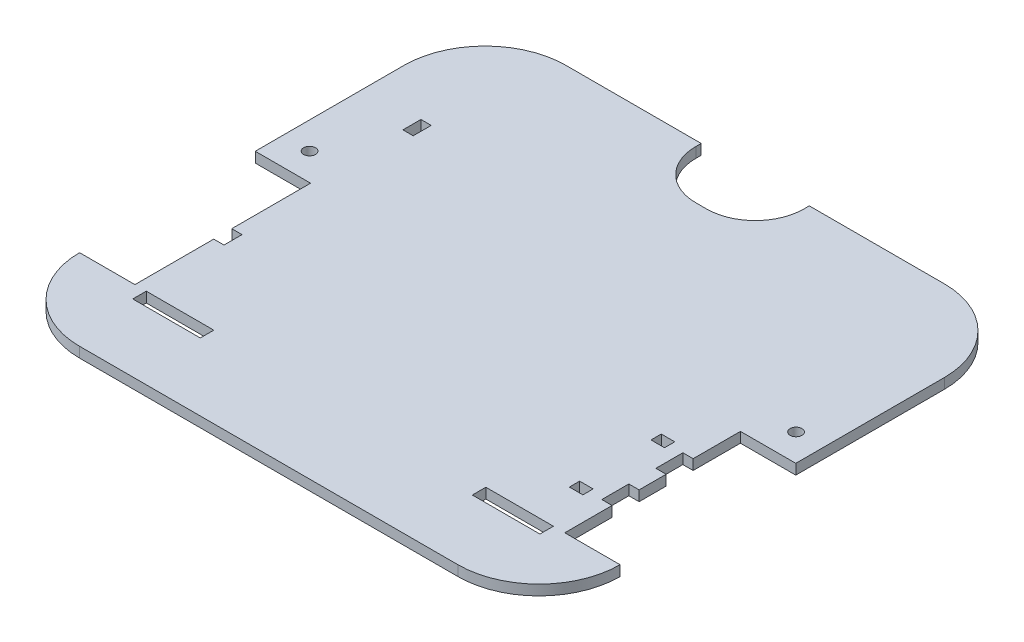
SolidWorks part; units mm, degrees
ref_plane "Front Plane" through (0, 0, 0) normal (0, 0, 1) x (1, 0, 0)
ref_plane "Top Plane" through (0, 0, 0) normal (0, 1, 0) x (1, 0, 0)
ref_plane "Right Plane" through (0, 0, 0) normal (1, 0, 0) x (0, 0, -1)
sketch "Sketch1" plane through (0, 0, 0) normal (0, 1, 0) x (1, 0, 0)
  line L1 (-127, 114.3) -> (127, 114.3)
  line L2 (-127, 114.3) -> (-127, -114.3)
  line L3 (-127, -114.3) -> (127, -114.3)
  line L4 (127, 114.3) -> (127, -114.3)
  line L5 (-127, 114.3) -> (127, -114.3) construction
  line L6 (-127, -114.3) -> (127, 114.3) construction
  point P0 (0, 0)
  dimension "D1" = 254
  dimension "D2" = 228.6
extrude "Boss-Extrude1" add sketch "Sketch1" along normal blind 4.826
sketch "Sketch2" plane through (0, 4.826, 0) normal (0, 1, 0) x (1, 0, 0)
  line L0 (-127, 114.3) -> (-127, -114.3) construction
  line L1 (-127, 6.35) -> (-101, 6.35)
  line L2 (-127, 6.35) -> (-127, -76.2)
  line L3 (-127, -76.2) -> (-101, -76.2)
  line L4 (-101, 6.35) -> (-101, -76.2)
  line L5 (127, -114.3) -> (127, 114.3) construction
  line L6 (127, 6.35) -> (101, 6.35)
  line L7 (127, 6.35) -> (127, -76.2)
  line L8 (127, -76.2) -> (101, -76.2)
  line L9 (101, 6.35) -> (101, -76.2)
  line L10 (-127, -114.3) -> (127, -114.3) construction
  dimension "D1" = 38.1
  dimension "D2" = 38.1
  dimension "D3" = 82.55
  dimension "D4" = 82.55
  dimension "D5" = 26
  dimension "D6" = 26
extrude "Cut-Extrude1" cut sketch "Sketch2" against normal blind 4.826
sketch "Sketch4" plane through (0, 4.826, 0) normal (0, 1, 0) x (1, 0, 0)
  line L0 (0, -114.3) -> (0, 114.3) construction
  line L1 (-127, -114.3) -> (127, -114.3) construction
  line L2 (127, 114.3) -> (-127, 114.3) construction
  line L3 (-127, 76.2) -> (-88.9, 76.2) construction
  line L4 (-127, 114.3) -> (-127, 6.35) construction
  line L5 (-88.9, 76.2) -> (-88.9, 114.3) construction
  line L6 (-127, 76.2) -> (-127, 114.3)
  line L7 (-127, 114.3) -> (-88.9, 114.3)
  line L8 (127, 76.2) -> (127, 114.3)
  line L9 (127, 114.3) -> (88.9, 114.3)
  arc A0 (-127, 76.2) -> (-88.9, 114.3) centre (-88.9, 76.2) cw
  arc A1 (127, 76.2) -> (88.9, 114.3) centre (88.9, 76.2) ccw
  dimension "D1" = 38.1
  dimension "D2" = 38.1
extrude "Cut-Extrude3" cut sketch "Sketch4" against normal blind 4.826
sketch "Sketch7" plane through (0, 4.826, 0) normal (0, 1, 0) x (1, 0, 0)
  line L0 (0, -114.3) -> (0, 114.3) construction
  line L1 (-127, -114.3) -> (127, -114.3) construction
  line L2 (88.9, 114.3) -> (-88.9, 114.3) construction
  line L3 (25.4, 88.9) -> (25.4, 114.3)
  line L4 (25.4, 88.9) -> (-25.4, 88.9)
  line L5 (0, 88.9) -> (0, 114.3)
  line L6 (25.4, 114.3) -> (-25.4, 114.3)
  line L7 (-25.4, 88.9) -> (-25.4, 114.3)
  line M6 (88.9, 114.3) -> (-88.9, 114.3)
extrude "Cut-Extrude5" cut sketch "Sketch7" against normal blind 4.826 contours L7 L4 L5 M6 | L5 L4 L3 M6 region at (12.7, 4.826, -101.6) region at (-12.7, 4.826, -101.6)
fillet "Fillet9" radius 22.86 1 edges at (-25.4, 2.413, -88.9) type face fillet first side face at (0, 2.413, -88.9) second side face at (-25.4, 2.413, -101.6)
fillet "Fillet10" radius 22.86 1 edges at (25.4, 2.413, -88.9) type face fillet first side face at (11.43, 2.413, -88.9) second side face at (25.4, 2.413, -101.6)
sketch "Sketch8" plane through (0, 4.826, 0) normal (0, 1, 0) x (1, 0, 0)
  line L0 (-127, -76.2) -> (-88.9, -76.2) construction
  line L1 (-88.9, -76.2) -> (-88.9, -114.3) construction
  line L2 (-127, -114.3) -> (127, -114.3) construction
  line L3 (-127, -76.2) -> (-127, -114.3)
  line L4 (-127, -114.3) -> (-88.9, -114.3)
  line L5 (0, -114.3) -> (0, 88.9) construction
  line L6 (2.54, 88.9) -> (-2.54, 88.9) construction
  line L7 (127, -114.3) -> (88.9, -114.3)
  line L8 (127, -76.2) -> (127, -114.3)
  arc A0 (-127, -76.2) -> (-88.9, -114.3) centre (-88.9, -76.2) ccw
  arc A1 (127, -76.2) -> (88.9, -114.3) centre (88.9, -76.2) cw
  dimension "D1" = 38.1
extrude "Cut-Extrude6" cut sketch "Sketch8" against normal blind 4.826
sketch "Sketch9" plane through (0, 0, 0) normal (0, -1, 0) x (1, 0, 0)
  line L0 (-58.582, 76.2) -> (-101, 76.2) construction
  line L1 (-95.666, 76.2) -> (-63.916, 76.2)
  line L2 (-95.666, 76.2) -> (-95.666, 82.55)
  line L3 (-95.666, 82.55) -> (-63.916, 82.55)
  line L4 (-63.916, 76.2) -> (-63.916, 82.55)
  line L5 (-101, 76.2) -> (-95.666, 76.2) construction
  line L6 (-63.916, 76.2) -> (-58.582, 76.2) construction
  line L7 (0, 114.3) -> (0, -88.9) construction
  line L8 (-88.9, 114.3) -> (88.9, 114.3) construction
  line L9 (2.54, -88.9) -> (-2.54, -88.9) construction
  line L10 (63.916, 76.2) -> (58.582, 76.2) construction
  line L11 (101, 76.2) -> (95.666, 76.2) construction
  line L12 (63.916, 76.2) -> (63.916, 82.55)
  line L13 (95.666, 82.55) -> (63.916, 82.55)
  line L14 (95.666, 76.2) -> (95.666, 82.55)
  line L15 (95.666, 76.2) -> (63.916, 76.2)
  dimension "D1" = 31.75
  dimension "D2" = 6.35
extrude "Cut-Extrude7" cut sketch "Sketch9" against normal through all
sketch "Sketch17" plane through (0, 0, 0) normal (0, -1, 0) x (1, 0, 0)
  circle A0 centre (114.3, -19.1646) radius 2.7781 construction
  circle A1 centre (-114.3, -19.1646) radius 2.7781 construction
  circle A2 centre (114.3, -19.1646) radius 2.7781
  circle A3 centre (-114.3, -19.1646) radius 2.7781
extrude "Cut-Extrude14" cut sketch "Sketch17" against normal through all
sketch "Sketch18" plane through (0, 4.826, 0) normal (0, 1, 0) x (1, 0, 0)
  line L0 (101, -53.975) -> (96.174, -53.975) construction
  line L1 (96.174, -41.275) -> (96.174, -53.975) construction
  line L2 (101, -41.275) -> (96.174, -41.275) construction
  line L3 (101, -41.275) -> (101, -53.975) construction
  line L4 (101, -15.875) -> (101, -28.575) construction
  line L5 (101, -15.875) -> (96.174, -15.875) construction
  line L6 (96.174, -15.875) -> (96.174, -28.575) construction
  line L7 (101, -28.575) -> (96.174, -28.575) construction
  line L8 (101, -53.975) -> (96.174, -53.975)
  line L9 (96.174, -41.275) -> (96.174, -53.975)
  line L10 (101, -41.275) -> (96.174, -41.275)
  line L11 (101, -41.275) -> (101, -53.975)
  line L12 (101, -15.875) -> (101, -28.575)
  line L13 (101, -15.875) -> (96.174, -15.875)
  line L14 (96.174, -15.875) -> (96.174, -28.575)
  line L15 (101, -28.575) -> (96.174, -28.575)
extrude "Cut-Extrude15" cut sketch "Sketch18" against normal through all
sketch "Sketch19" plane through (0, 4.826, 0) normal (0, 1, 0) x (1, 0, 0)
  line L0 (-101, -39.1583) -> (-101, -30.6917) construction
  line L1 (-101, -39.1583) -> (-96.174, -39.1583) construction
  line L2 (-96.174, -39.1583) -> (-96.174, -30.6917) construction
  line L3 (-101, -30.6917) -> (-96.174, -30.6917) construction
  line L4 (-101, 49.7417) -> (-101, 58.2083) construction
  line L5 (-101, 49.7417) -> (-96.174, 49.7417) construction
  line L6 (-96.174, 49.7417) -> (-96.174, 58.2083) construction
  line L7 (-101, 58.2083) -> (-96.174, 58.2083) construction
  line L8 (-101, -39.1583) -> (-101, -30.6917)
  line L9 (-101, -39.1583) -> (-96.174, -39.1583)
  line L10 (-96.174, -39.1583) -> (-96.174, -30.6917)
  line L11 (-101, -30.6917) -> (-96.174, -30.6917)
  line L12 (-101, 49.7417) -> (-101, 58.2083)
  line L13 (-101, 49.7417) -> (-96.174, 49.7417)
  line L14 (-96.174, 49.7417) -> (-96.174, 58.2083)
  line L15 (-101, 58.2083) -> (-96.174, 58.2083)
extrude "Cut-Extrude16" cut sketch "Sketch19" against normal through all
sketch "Sketch20" plane through (0, 0, 0) normal (0, -1, 0) x (1, 0, 0)
  line L0 (83.474, 51.689) -> (89.824, 51.689) construction
  line L1 (83.474, 56.515) -> (83.474, 51.689) construction
  line L2 (83.474, 56.515) -> (89.824, 56.515) construction
  line L3 (89.824, 56.515) -> (89.824, 51.689) construction
  line L4 (83.474, 13.335) -> (89.824, 13.335) construction
  line L5 (83.474, 18.161) -> (83.474, 13.335) construction
  line L6 (83.474, 18.161) -> (89.824, 18.161) construction
  line L7 (89.824, 18.161) -> (89.824, 13.335) construction
  line L8 (83.474, 51.689) -> (89.824, 51.689)
  line L9 (83.474, 56.515) -> (83.474, 51.689)
  line L10 (83.474, 56.515) -> (89.824, 56.515)
  line L11 (89.824, 56.515) -> (89.824, 51.689)
  line L12 (83.474, 13.335) -> (89.824, 13.335)
  line L13 (83.474, 18.161) -> (83.474, 13.335)
  line L14 (83.474, 18.161) -> (89.824, 18.161)
  line L15 (89.824, 18.161) -> (89.824, 13.335)
extrude "Cut-Extrude17" cut sketch "Sketch20" against normal blind 4.826
equation "\"MDF\"= 0.19in"
equation "\"GenDiameter\"= 60mm"
equation "\"GenCutDiameter\" = 1.8in"
equation "\"GenCutDistance\" = 1"
equation "\"TowerHeight\" = 6in"
equation "\"TowerFrontBase\" = 3in"
equation "\"FunnelHeight\" = 1in"
equation "\"FunnelAngle\" = 20"
equation "\"TowerSideBase\" = 3in"
equation "\"BaseLength\" = 9in"
equation "\"BaseWidth\" = 10in"
equation "\"WheelHoleLength\" = 3.25in"
equation "\"WheelHoleWidth\" = 26mm"
equation "\"DropLength\" = 1in"
equation "\"D1@Sketch1\"=\"BaseWidth\""
equation "\"D2@Sketch1\"=\"BaseLength\""
equation "\"D1@Boss-Extrude1\"=\"MDF\""
equation "\"WheelHoleFromBack\" = 1.5in"
equation "\"D1@Sketch2\"=\"WheelHoleFromBack\""
equation "\"D2@Sketch2\"=\"WheelHoleFromBack\""
equation "\"D3@Sketch2\"=\"WheelHoleLength\""
equation "\"D4@Sketch2\"=\"WheelHoleLength\""
equation "\"D5@Sketch2\"=\"WheelHoleWidth\""
equation "\"D6@Sketch2\"=\"WheelHoleWidth\""
equation "\"D1@Cut-Extrude1\"=\"MDF\""
equation "\"DropWidth\" = 8.5in"
equation "\"BumperWidth\" = 2in"
equation "\"D1@Cut-Extrude3\"=\"MDF\""
equation "\"D1@Sketch7\"=\"DropLength\""
equation "\"D1@Cut-Extrude5\"=\"MDF\""
equation "\"D1@Cut-Extrude6\"=\"MDF\""
equation "\"DropWidthTop\" = 0in"
equation "\"D1@Cut-Extrude17\"=\"MDF\""
